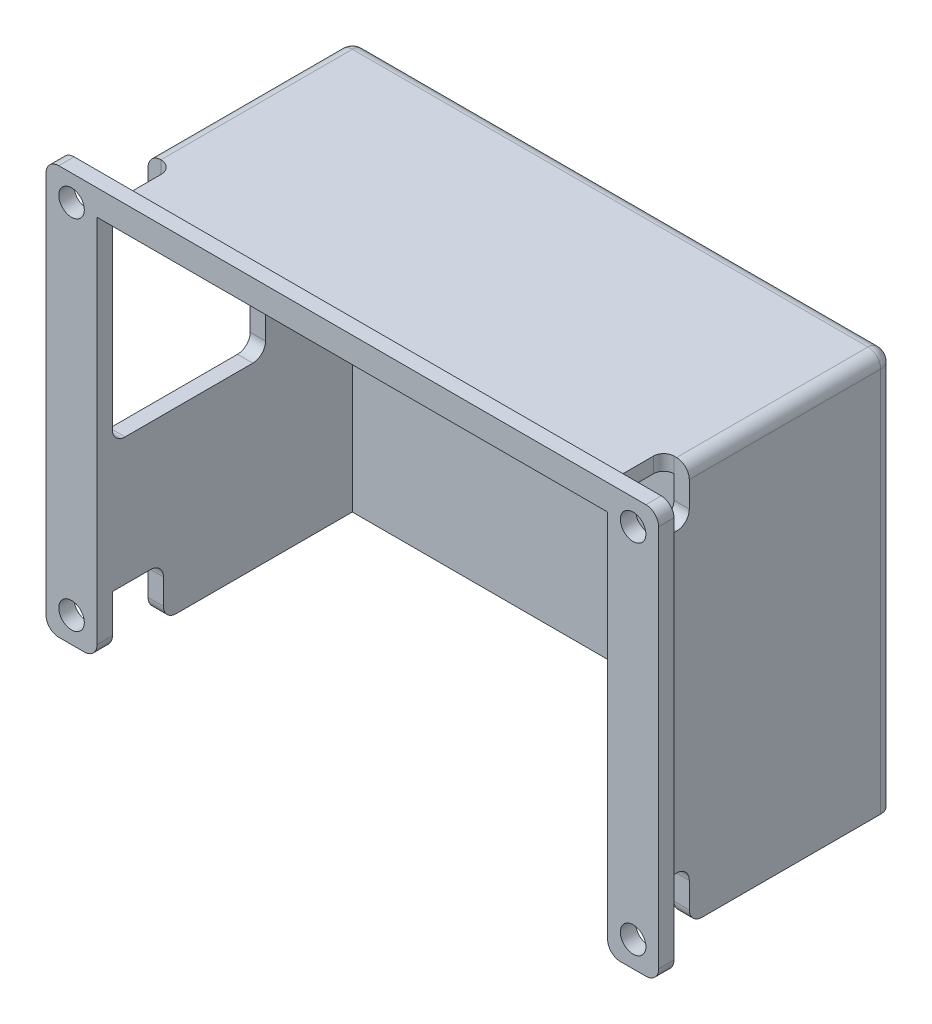
SolidWorks part; units mm, degrees
ref_plane "Front Plane" through (0, 0, 0) normal (0, 0, 1) x (1, 0, 0)
ref_plane "Top Plane" through (0, 0, 0) normal (0, 1, 0) x (1, 0, 0)
ref_plane "Right Plane" through (0, 0, 0) normal (1, 0, 0) x (0, 0, -1)
sketch "Sketch2" plane through (0, 0, 0) normal (0, 0, 1) x (1, 0, 0)
  line L1 (15.306, 62.8336) -> (75.306, 62.8336)
  line L2 (15.306, 62.8336) -> (15.306, 22.8336)
  line L3 (15.306, 22.8336) -> (75.306, 22.8336)
  line L4 (75.306, 62.8336) -> (75.306, 22.8336)
  circle A0 centre (17.806, 60.3336) radius 1.25
  circle A1 centre (17.806, 25.3336) radius 1.25
  circle A2 centre (72.806, 25.3336) radius 1.25
  circle A3 centre (72.806, 60.3336) radius 1.25
  dimension "D2" = 2.5
  dimension "D1" = 60
  dimension "D3" = 40
  dimension "D4" = 2.5
  dimension "D5" = 2.5
  dimension "D6" = 2.5
  dimension "D7" = 2.5
extrude "Boss-Extrude3" add sketch "Sketch2" along normal blind 1.5
sketch "Sketch3" plane through (0, 0, 0) normal (0, 0, -1) x (-1, 0, 0)
  line L0 (-75.306, 62.8336) -> (-15.306, 62.8336) construction
  line L1 (-71.806, 61.8336) -> (-18.806, 61.8336)
  line L2 (-71.806, 61.8336) -> (-71.806, 22.8336)
  line L3 (-71.806, 22.8336) -> (-18.806, 22.8336)
  line L4 (-18.806, 61.8336) -> (-18.806, 22.8336)
  line L6 (-15.306, 22.8336) -> (-75.306, 22.8336) construction
  line L7 (-75.306, 22.8336) -> (-75.306, 62.8336) construction
  line L8 (-15.306, 62.8336) -> (-15.306, 22.8336) construction
  dimension "D1" = 1
  dimension "D2" = 0
  dimension "D3" = 3.5
  dimension "D4" = 3.5
extrude "Boss-Extrude4" add sketch "Sketch3" along normal blind 25
sketch "Sketch7" plane through (0, 0, 1.5) normal (0, 0, 1) x (1, 0, 0)
  line L0 (75.306, 62.8336) -> (15.306, 62.8336) construction
  line L1 (20.306, 60.3336) -> (70.306, 60.3336)
  line L2 (20.306, 60.3336) -> (20.306, 22.8336)
  line L3 (20.306, 22.8336) -> (70.306, 22.8336)
  line L4 (70.306, 60.3336) -> (70.306, 22.8336)
  line L5 (15.306, 62.8336) -> (15.306, 22.8336) construction
  line L6 (75.306, 22.8336) -> (75.306, 62.8336) construction
  line L7 (15.306, 22.8336) -> (75.306, 22.8336) construction
  dimension "D1" = 2.5
  dimension "D2" = 5
  dimension "D3" = 5
  dimension "D4" = 0
extrude "Cut-Extrude4" cut sketch "Sketch7" against normal blind 25
sketch "Sketch8" plane through (71.806, 0, 0) normal (1, 0, 0) x (0, 0, -1)
  line L0 (25, 61.8336) -> (0, 61.8336) construction
  line L1 (0, 61.8336) -> (5, 61.8336)
  line L2 (0, 61.8336) -> (0, 56.8336)
  line L3 (0, 56.8336) -> (5, 56.8336)
  line L4 (5, 61.8336) -> (5, 56.8336)
  line L6 (0, 24.5836) -> (0, 22.8336) construction
  line L8 (0, 22.8336) -> (5, 22.8336)
  line L9 (0, 22.8336) -> (0, 27.8336)
  line L10 (0, 27.8336) -> (5, 27.8336)
  line L11 (5, 22.8336) -> (5, 27.8336)
  dimension "D1" = 5
  dimension "D2" = 5
extrude "Cut-Extrude5" cut sketch "Sketch8" against normal blind 2.5
sketch "Sketch11" plane through (18.806, 0, 0) normal (-1, 0, 0) x (0, 0, 1)
  line L1 (0, 62.8336) -> (-5, 62.8336)
  line L2 (0, 62.8336) -> (0, 57.8336)
  line L3 (0, 57.8336) -> (-5, 57.8336)
  line L4 (-5, 62.8336) -> (-5, 57.8336)
  line L5 (0, 22.8336) -> (-5, 22.8336)
  line L6 (0, 22.8336) -> (0, 27.8336)
  line L7 (0, 27.8336) -> (-5, 27.8336)
  line L8 (-5, 22.8336) -> (-5, 27.8336)
  dimension "D1" = 5
  dimension "D2" = 5
extrude "Cut-Extrude8" cut sketch "Sketch11" against normal blind 2.5
sketch "Sketch15" plane through (0, 0, -23.5) normal (0, 0, 1) x (1, 0, 0)
  line L1 (70.306, 22.8336) -> (52.306, 22.8336)
  line L2 (70.306, 22.8336) -> (70.306, 32.8336)
  line L3 (70.306, 32.8336) -> (52.306, 32.8336)
  line L4 (52.306, 22.8336) -> (52.306, 32.8336)
  dimension "D1" = 18
  dimension "D2" = 10
extrude "Cut-Extrude12" cut sketch "Sketch15" against normal blind 2.5
sketch "Sketch17" plane through (18.806, 0, 0) normal (-1, 0, 0) x (0, 0, 1)
  line L1 (-15, 40.3336) -> (0, 40.3336)
  line L2 (-15, 40.3336) -> (-15, 57.8336)
  line L3 (-15, 57.8336) -> (0, 57.8336)
  line L4 (0, 40.3336) -> (0, 57.8336)
  line L5 (0, 27.8336) -> (0, 57.8336) construction
  line L6 (1.5, 62.8336) -> (0, 62.8336) construction
  dimension "D1" = 5
  dimension "D2" = 17.5
  dimension "D3" = 15
extrude "Cut-Extrude13" cut sketch "Sketch17" against normal blind 2.5
fillet "Fillet11" radius 1.25 7 edges at (19.556, 57.8336, -5) (19.556, 57.8336, -15) (19.556, 40.3336, -15) (19.556, 40.3336, 0) (70.306, 32.8336, -24.25) (52.306, 22.8336, -24.25) (52.306, 32.8336, -24.25)
fillet "Fillet13" radius 1.25 12 edges at (71.056, 56.8336, -5) (21.306, 61.0836, -5) (71.056, 22.8336, -5) (71.056, 27.8336, -5) (19.556, 27.8336, -5) (19.556, 22.8336, -5) (75.306, 62.8336, 0.75) (15.306, 62.8336, 0.75) (75.306, 22.8336, 0.75) (70.306, 22.8336, 0.75) (20.306, 22.8336, 0.75) (15.306, 22.8336, 0.75)
fillet "Fillet14" radius 1 1 edges at (69.306, 61.0836, -5)
fillet "Fillet15" radius 1.25 5 edges at (18.806, 61.8336, -15) (71.806, 61.8336, -15) (18.806, 42.3336, -25) (45.306, 61.8336, -25) (71.806, 42.3336, -25)
